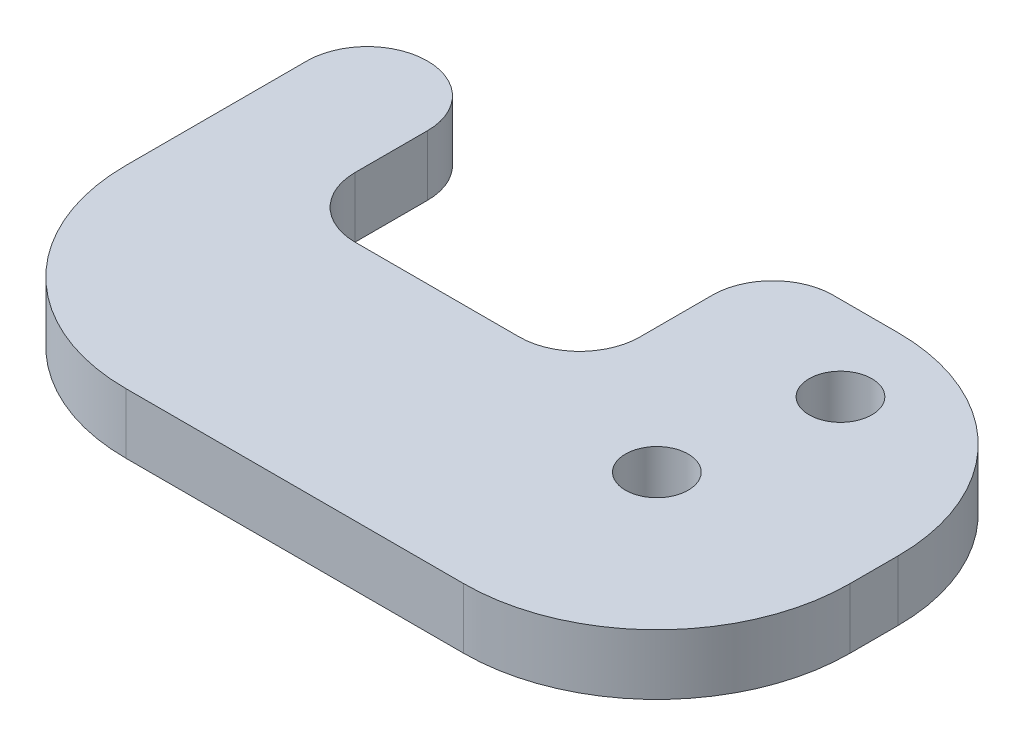
SolidWorks part; units mm, degrees
ref_plane "Front Plane" through (0, 0, 0) normal (0, 0, 1) x (1, 0, 0)
ref_plane "Top Plane" through (0, 0, 0) normal (0, 1, 0) x (1, 0, 0)
ref_plane "Right Plane" through (0, 0, 0) normal (1, 0, 0) x (0, 0, -1)
sketch "Sketch1" plane through (0, 0, 0) normal (0, 1, 0) x (1, 0, 0)
  line L1 (-19.05, 11.43) -> (19.05, 11.43)
  line L2 (-19.05, 11.43) -> (-19.05, -11.43)
  line L3 (-19.05, -11.43) -> (19.05, -11.43)
  line L4 (19.05, 11.43) -> (19.05, -11.43)
  dimension "D1" = 22.86
  dimension "D2" = 38.1
  dimension "D3" = 11.43
  dimension "D4" = 19.05
extrude "Boss-Extrude1" add sketch "Sketch1" along normal blind 3.175
fillet "Fillet1" radius 10.16 2 edges at (-19.05, 1.5875, 11.43) (19.05, 1.5875, 11.43)
sketch "Sketch3" plane through (0, 3.175, 0) normal (0, 1, 0) x (1, 0, 0)
  line L0 (-7.7526, -1.27) -> (18.5521, -1.27) construction
  circle A0 centre (8.89, -1.27) radius 1.651
  circle A1 centre (10.287, 6.9948) radius 1.651
  arc A2 (8.89, -11.43) -> (19.05, -1.27) centre (8.89, -1.27) ccw construction
  circle A3 centre (-7.874, -1.27) radius 1.651
  dimension "D1" = 3.302
  dimension "D2" = 3.302
  dimension "D6" = 3.302
  dimension "D3" = 8.382
  dimension "D4" = 1.397
  dimension "D5" = 16.764
extrude "Cut-Extrude1" cut sketch "Sketch3" against normal through all contours A0 | A1
fillet "Fillet3" radius 10.16 1 edges at (19.05, 1.5875, -11.43)
sketch "Sketch4" plane through (0, 3.175, 0) normal (0, 1, 0) x (1, 0, 0)
  line L1 (-12.7, 11.43) -> (2.286, 11.43)
  line L2 (-12.7, 11.43) -> (-12.7, 1.27)
  line L3 (-8.89, -11.43) -> (8.89, -11.43) construction
  line L4 (2.286, 11.43) -> (2.286, 1.27)
  line L5 (19.05, -1.27) -> (19.05, 1.27) construction
  line L8 (8.89, 11.43) -> (-19.05, 11.43) construction
  line L12 (-12.7, 1.27) -> (2.286, 1.27)
  line L13 (-19.05, 11.43) -> (-19.05, -1.27) construction
  dimension "D1" = 16.764
  dimension "D2" = 12.7
  dimension "D3" = 6.35
extrude "Cut-Extrude3" cut sketch "Sketch4" against normal through all contours L1 L4 L12 L2
fillet "Fillet8" radius 3.175 5 edges at (-12.7, 1.5875, -1.27) (2.286, 1.5875, -1.27) (2.286, 1.5875, -11.43) (-12.7, 1.5875, -11.43) (-19.05, 1.5875, -11.43)
equation "\"D4@Sketch1\"=\"D2@Sketch1\"/2"
equation "\"D3@Sketch1\"=\"D1@Sketch1\"/2"
